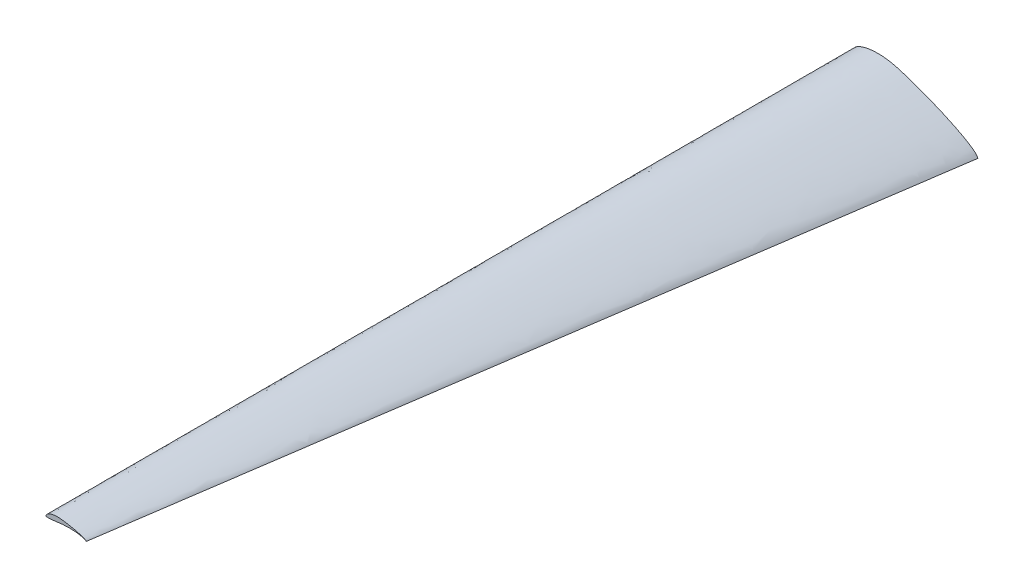
SolidWorks part; units mm, degrees
ref_plane "Front Plane" through (0, 0, 0) normal (0, 0, 1) x (1, 0, 0)
ref_plane "Top Plane" through (0, 0, 0) normal (0, 1, 0) x (1, 0, 0)
ref_plane "Right Plane" through (0, 0, 0) normal (1, 0, 0) x (0, 0, -1)
curve "Curve3"
  spline degree 3 poles (9.9613, 0.026, 0) (10.0091, -0.0065, 0) (9.9672, 0.0247, 0) (9.9394, 0.052, 0) (9.8777, 0.109, 0) (9.8048, 0.1696, 0) (9.7052, 0.2307, 0) (9.5813, 0.2899, 0) (9.4318, 0.3517, 0) (9.2568, 0.4153, 0) (9.0571, 0.4801, 0) (8.8339, 0.5456, 0) (8.5883, 0.6115, 0) (8.3218, 0.6772, 0) (8.0358, 0.7422, 0) (7.732, 0.8062, 0) (7.4124, 0.8687, 0) (7.0787, 0.9291, 0) (6.7331, 0.9871, 0) (6.3775, 1.0422, 0) (6.0143, 1.0944, 0) (5.6458, 1.1432, 0) (5.2747, 1.1886, 0) (4.9038, 1.2308, 0) (4.5364, 1.2688, 0) (4.1754, 1.3018, 0) (3.8233, 1.3281, 0) (3.4821, 1.3462, 0) (3.1538, 1.354, 0) (2.84, 1.3531, 0) (2.5413, 1.3378, 0) (2.2576, 1.3066, 0) (1.9877, 1.2626, 0) (1.7316, 1.2056, 0) (1.4895, 1.1387, 0) (1.2625, 1.0631, 0) (1.0515, 0.9807, 0) (0.8578, 0.8918, 0) (0.6821, 0.7983, 0) (0.5253, 0.7011, 0) (0.3884, 0.6017, 0) (0.2714, 0.5022, 0) (0.1761, 0.4014, 0) (0.1029, 0.3002, 0) (0.0488, 0.2017, 0) (0.0142, 0.1083, 0) (-0.0023, 0.022, 0) (0.0009, -0.051, 0) (0.0196, -0.1179, 0) (0.0895, -0.1511, 0) (0.1833, -0.1558, 0) (0.3118, -0.1603, 0) (0.4733, -0.1533, 0) (0.666, -0.1405, 0) (0.8879, -0.12, 0) (1.1366, -0.0923, 0) (1.4109, -0.0567, 0) (1.7108, -0.007, 0) (2.0375, 0.0554, 0) (2.3929, 0.1232, 0) (2.7751, 0.1948, 0) (3.1818, 0.2673, 0) (3.6099, 0.3378, 0) (4.0561, 0.4041, 0) (4.5167, 0.4637, 0) (4.9874, 0.5149, 0) (5.4638, 0.5554, 0) (5.9411, 0.584, 0) (6.4144, 0.5998, 0) (6.8785, 0.6018, 0) (7.3282, 0.5899, 0) (7.7584, 0.5643, 0) (8.1638, 0.5255, 0) (8.5398, 0.4748, 0) (8.8813, 0.4138, 0) (9.1845, 0.3445, 0) (9.4436, 0.2704, 0) (9.6556, 0.1913, 0) (9.8069, 0.1188, 0) (9.9185, 0.0519, 0) (9.9613, 0.026, 0) (10.0091, -0.0065, 0) (9.9672, 0.0247, 0) knots -0.009748 -0.004147 -0.001 0 0.00098 0.003649 0.007483 0.012095 0.017526 0.024052 0.031783 0.040678 0.05071 0.061833 0.073989 0.087118 0.101145 0.115991 0.13157 0.147788 0.164551 0.181758 0.199312 0.217095 0.23499 0.252857 0.270541 0.287887 0.304773 0.321101 0.336806 0.3518 0.366031 0.379616 0.392653 0.40517 0.417172 0.428604 0.439419 0.449597 0.459102 0.467908 0.475988 0.483309 0.489875 0.495803 0.501149 0.505903 0.510047 0.513579 0.516447 0.51935 0.523823 0.529974 0.537716 0.546968 0.557637 0.56962 0.582804 0.597247 0.613135 0.630444 0.649056 0.668822 0.689595 0.71119 0.733427 0.756094 0.778989 0.80189 0.824567 0.846792 0.868338 0.888978 0.908492 0.926659 0.943286 0.958169 0.971136 0.981956 0.990252 0.995853 0.999 1 1.00098 1.003649 1.007483 periodic
sketch "Sketch6" plane through (0, 0, 0) normal (0, 0, 1) x (1, 0, 0)
  spline S1 degree 3 poles (77.3735, -19.0773) (77.6815, -19.4214) (77.4168, -19.0981) (77.2538, -18.8326) (76.8849, -18.2708) (76.4369, -17.6594) (75.7818, -16.9923) (74.9348, -16.2929) (73.8935, -15.5237) (72.658, -14.6919) (71.2338, -13.8026) (69.6279, -12.8621) (67.8493, -11.8752) (65.9074, -10.8493) (63.8132, -9.7909) (61.5791, -8.7066) (59.2188, -7.6025) (56.7454, -6.4882) (54.175, -5.3684) (51.5216, -4.2528) (48.8033, -3.1449) (46.0374, -2.0526) (43.2442, -0.9822) (40.4475, 0.0631) (37.6689, 1.0691) (34.9304, 2.0244) (32.248, 2.9097) (29.6348, 3.7102) (27.1012, 4.4062) (24.6637, 5.0071) (22.3154, 5.4659) (20.0528, 5.7733) (17.8727, 5.9539) (15.7743, 6.0068) (13.7658, 5.9561) (11.8573, 5.8091) (10.0599, 5.5775) (8.3846, 5.2623) (6.8396, 4.8762) (5.4345, 4.4257) (4.1794, 3.9191) (3.0789, 3.3727) (2.1439, 2.7746) (1.3798, 2.1308) (0.7695, 1.4714) (0.3196, 0.8129) (0.0244, 0.1753) (-0.092, -0.3973) (-0.0757, -0.9531) (0.402, -1.3461) (1.1217, -1.5639) (2.1099, -1.8475) (3.377, -2.1061) (4.8981, -2.3798) (6.66, -2.65) (8.6442, -2.9161) (10.8425, -3.1709) (13.2661, -3.3653) (15.9233, -3.5138) (18.8131, -3.6748) (21.9185, -3.8585) (25.2154, -4.0831) (28.6751, -4.364) (32.2674, -4.7131) (35.9577, -5.1418) (39.7106, -5.6555) (43.4869, -6.2635) (47.2476, -6.9647) (50.9518, -7.7583) (54.558, -8.641) (58.0257, -9.6038) (61.3154, -10.6347) (64.3877, -11.721) (67.208, -12.8419) (69.7411, -13.9764) (71.9599, -15.1009) (73.8277, -16.1779) (75.3206, -17.2026) (76.3548, -18.0575) (77.0911, -18.7932) (77.3735, -19.0773) (77.6815, -19.4214) (77.4168, -19.0981) knots -0.009748 -0.004147 -0.001 0 0.00098 0.003649 0.007483 0.012095 0.017526 0.024052 0.031783 0.040678 0.05071 0.061833 0.073989 0.087118 0.101145 0.115991 0.13157 0.147788 0.164551 0.181758 0.199312 0.217095 0.23499 0.252857 0.270541 0.287887 0.304773 0.321101 0.336806 0.3518 0.366031 0.379616 0.392653 0.40517 0.417172 0.428604 0.439419 0.449597 0.459102 0.467908 0.475988 0.483309 0.489875 0.495803 0.501149 0.505903 0.510047 0.513579 0.516447 0.51935 0.523823 0.529974 0.537716 0.546968 0.557637 0.56962 0.582804 0.597247 0.613135 0.630444 0.649056 0.668822 0.689595 0.71119 0.733427 0.756094 0.778989 0.80189 0.824567 0.846792 0.868338 0.888978 0.908492 0.926659 0.943286 0.958169 0.971136 0.981956 0.990252 0.995853 0.999 1 1.00098 1.003649 1.007483 only from (77.6237, -19.3538) to (77.6237, -19.3538)
ref_plane "Plane1" through (0, 0, 500) normal (0, 0, 1) x (1, 0, 0)
sketch "Sketch8" plane through (0, 0, 500) normal (0, 0, 1) x (1, 0, 0)
  spline S2 degree 3 poles (24.8725, -1.2385) (24.9875, -1.3257) (24.8871, -1.2423) (24.8212, -1.1706) (24.6746, -1.0203) (24.5007, -0.8594) (24.2599, -0.6938) (23.9584, -0.5298) (23.5931, -0.3559) (23.1645, -0.1744) (22.6746, 0.0135) (22.1259, 0.2062) (21.5214, 0.4029) (20.8646, 0.6018) (20.159, 0.8016) (19.4091, 1.001) (18.6192, 1.1989) (17.794, 1.3933) (16.9387, 1.5835) (16.0583, 1.7675) (15.1584, 1.9453) (14.2447, 2.1155) (13.3241, 2.2773) (12.4038, 2.4312) (11.4915, 2.5741) (10.5945, 2.7038) (9.7189, 2.8155) (8.8695, 2.9052) (8.0508, 2.9676) (7.2673, 3.0066) (6.5195, 3.0073) (5.8071, 2.9667) (5.1276, 2.8921) (4.4807, 2.7832) (3.8676, 2.6479) (3.291, 2.489) (2.7534, 2.3108) (2.2583, 2.1142) (1.8074, 1.9037) (1.4032, 1.6817) (1.0484, 1.4514) (0.7434, 1.2182) (0.4922, 0.979) (0.2962, 0.7359) (0.1483, 0.4972) (0.0496, 0.2684) (-0.003, 0.0552) (-0.0045, -0.1274) (0.0336, -0.2969) (0.2036, -0.3889) (0.4373, -0.4129) (0.7574, -0.4409) (1.1615, -0.4447) (1.6444, -0.438) (2.201, -0.4158) (2.8256, -0.3791) (3.5151, -0.3262) (4.2701, -0.2413) (5.0941, -0.1284) (5.9902, -0.0055) (6.9538, 0.1233) (7.9785, 0.251) (9.0566, 0.3711) (10.1793, 0.4783) (11.3369, 0.5668) (12.5188, 0.633) (13.7135, 0.6716) (14.9089, 0.6808) (16.0925, 0.6582) (17.2514, 0.6025) (18.3725, 0.5139) (19.4431, 0.3938) (20.4504, 0.2438) (21.3824, 0.0681) (22.2271, -0.1289) (22.9747, -0.3415) (23.6119, -0.5605) (24.131, -0.7858) (24.4992, -0.9864) (24.7689, -1.1682) (24.8725, -1.2385) (24.9875, -1.3257) (24.8871, -1.2423) knots -0.009748 -0.004147 -0.001 0 0.00098 0.003649 0.007483 0.012095 0.017526 0.024052 0.031783 0.040678 0.05071 0.061833 0.073989 0.087118 0.101145 0.115991 0.13157 0.147788 0.164551 0.181758 0.199312 0.217095 0.23499 0.252857 0.270541 0.287887 0.304773 0.321101 0.336806 0.3518 0.366031 0.379616 0.392653 0.40517 0.417172 0.428604 0.439419 0.449597 0.459102 0.467908 0.475988 0.483309 0.489875 0.495803 0.501149 0.505903 0.510047 0.513579 0.516447 0.51935 0.523823 0.529974 0.537716 0.546968 0.557637 0.56962 0.582804 0.597247 0.613135 0.630444 0.649056 0.668822 0.689595 0.71119 0.733427 0.756094 0.778989 0.80189 0.824567 0.846792 0.868338 0.888978 0.908492 0.926659 0.943286 0.958169 0.971136 0.981956 0.990252 0.995853 0.999 1 1.00098 1.003649 1.007483 only from (24.9657, -1.3084) to (24.9657, -1.3084)
sketch3d "3DSketch1"
  line L0 (24.9657, -1.3084, 500) -> (77.6237, -19.3538, 0)
loft "Loft2" add profiles "Sketch6", "Sketch8" connector at (77.5896, -19.3091, 0) connector at (24.9657, -1.3084, 500)
